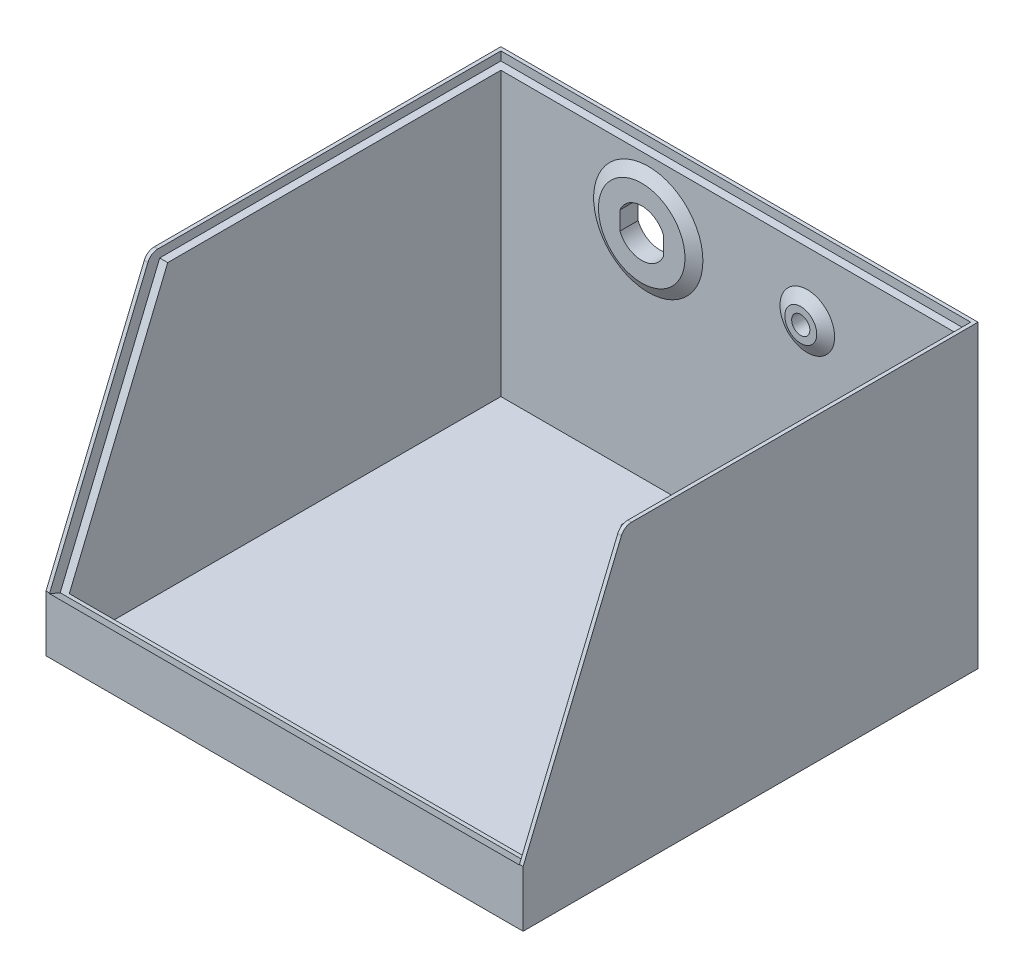
SolidWorks part; units mm, degrees
note: The reader was unsure of these and kept them because the rebuilt part matched: shared geometry of "Sketch1<3>".
material "ABS"
ref_plane "Front Plane" through (0, 0, 0) normal (0, 0, 1) x (1, 0, 0)
ref_plane "Top Plane" through (0, 0, 0) normal (0, 1, 0) x (1, 0, 0)
ref_plane "Right Plane" through (0, 0, 0) normal (1, 0, 0) x (0, 0, -1)
sketch "Sketch1" plane through (0, 0, 0) normal (0, 1, 0) x (1, 0, 0)
  line L0 (-3.2, 123.1151) -> (127.8, 123.1151)
  line L1 (0, 1.4151) -> (124.6, 1.4151)
  line L2 (0, 1.4151) -> (0, 119.9151)
  line L3 (0, 119.9151) -> (124.6, 119.9151)
  line L4 (124.6, 1.4151) -> (124.6, 119.9151)
  line L5 (127.8, -1.7849) -> (127.8, 123.1151)
  line L6 (-3.2, -1.7849) -> (127.8, -1.7849)
  line L7 (-3.2, -1.7849) -> (-3.2, 123.1151)
  dimension "D1" = 118.5
  dimension "D2" = 131
  dimension "D3" = 3.2
extrude "Boss-Extrude1" add sketch "Sketch1" against normal blind 2.4 contours L1 L4 L3 L2 | L7 L6 L5 L0 L4 L1 L2 L3
extrude "Boss-Extrude2" add sketch "Sketch1<3>" along normal blind 80
sketch "Sketch1<3>" plane through (0, 0, 0) normal (0, 1, 0) x (1, 0, 0) same geometry as "Sketch1"
sketch "Sketch2" plane through (127.8, 0, 0) normal (1, 0, 0) x (0, 0, -1)
  line L0 (-1.7849, 13.0187) -> (25.9596, 80)
  line L1 (-1.7849, -2.4) -> (-1.7849, 80) construction
  line L2 (-1.7849, 80) -> (123.1151, 80) construction
  line L3 (25.9596, 80) -> (-1.7849, 80)
  line L4 (-1.7849, 80) -> (-1.7849, 13.0187)
  dimension "D1" = 72.5
  dimension "D2" = 22.5
extrude "Cut-Extrude1" cut sketch "Sketch2" against normal through all
sketch "Sketch3" plane through (0, 2.5376, 6.1263) normal (0, 0.3827, 0.9239) x (1, 0, 0)
  line L0 (124.6, 19.7067) -> (0, 19.7067) construction
  line L1 (0, 19.7067) -> (124.6, 19.7067)
  line L2 (0, 19.7067) -> (0, 16.3447)
  line L3 (0, 16.3447) -> (124.6, 16.3447)
  line L4 (124.6, 19.7067) -> (124.6, 16.3447)
  line L5 (124.6, 83.8447) -> (124.6, 19.7067) construction
  line L6 (-3.2, 11.3447) -> (127.8, 11.3447) construction
  dimension "D1" = 5
extrude "Cut-Extrude2" cut sketch "Sketch3" against normal up to next
sketch "Sketch4" plane through (0, 2.5376, 6.1263) normal (0, 0.3827, 0.9239) x (1, 0, 0)
  line L0 (-3.2, 83.8447) -> (0, 83.8447) construction
  line L1 (-2.2, 83.8447) -> (126.8, 83.8447)
  line L2 (-2.2, 83.8447) -> (-2.2, 11.1947)
  line L3 (-2.2, 11.1947) -> (126.8, 11.1947)
  line L4 (126.8, 83.8447) -> (126.8, 11.1947)
  line L5 (-3.2, 11.3447) -> (127.8, 11.3447) construction
  point P6 (62.3, 11.1947)
  point P9 (62.3, 11.3447)
  dimension "D1" = 129
  dimension "D2" = 72.65
extrude "Cut-Extrude3" cut sketch "Sketch4" against normal blind 3.2
sketch "Sketch5" plane through (0, 80, 0) normal (0, 1, 0) x (1, 0, 0)
  line L0 (127.8, 25.9596) -> (127.8, 123.1151) construction
  line L1 (-2.2, 25.9596) -> (126.8, 25.9596)
  line L2 (-2.2, 25.9596) -> (-2.2, 122.1151)
  line L3 (-2.2, 122.1151) -> (126.8, 122.1151)
  line L4 (126.8, 25.9596) -> (126.8, 122.1151)
  line L5 (127.8, 123.1151) -> (-3.2, 123.1151) construction
  dimension "D1" = 1
  dimension "D2" = 1
  dimension "D3" = 129
extrude "Cut-Extrude4" cut sketch "Sketch5" against normal blind 2.4
fillet "Fillet1" radius 3 2 edges at (127.3, 80, -25.9596) (-2.7, 80, -25.9596)
sketch "Sketch6" plane through (0, 0, -123.1151) normal (0, 0, -1) x (-1, 0, 0)
  line L0 (-127.8, 60) -> (3.2, 60) construction
  line L3 (-46.4611, 62.5196) -> (-34.4723, 62.5196)
  line L4 (-46.4611, 62.5196) -> (-46.4611, 57.4804)
  line L5 (-46.4611, 57.4804) -> (-34.4723, 57.4804)
  line L6 (-34.4723, 62.5196) -> (-34.4723, 57.4804)
  line L7 (-127.8, -2.4) -> (-127.8, 80) construction
  line L8 (3.2, -2.4) -> (3.2, 80) construction
  line L9 (-127.8, 80) -> (3.2, 80) construction
  circle A2 centre (-40.4667, 60) radius 6.5024
  circle A3 centre (-84.1333, 60) radius 2.5
  dimension "D1" = 13.0048
  dimension "D2" = 11.9888
  dimension "D4" = 5
  dimension "D3" = 20
  dimension "D5" = 43.6667
  dimension "D6" = 43.6667
  dimension "D7" = 43.6667
sketch "Sketch7" plane through (0, 0, -119.9151) normal (0, 0, 1) x (1, 0, 0)
  circle A0 centre (40.4667, 60) radius 15
  circle A1 centre (84.1333, 60) radius 7.5
  dimension "D1" = 30
  dimension "D2" = 15
extrude "Boss-Extrude3" add sketch "Sketch7" along normal offset from surface 5 draft 60
extrude "Cut-Extrude6" cut sketch "Sketch6" against normal through all contours L5 A2 | L0 L4 L5 L6 | L4 L0 L6 L3 | L3 A2 | A3
